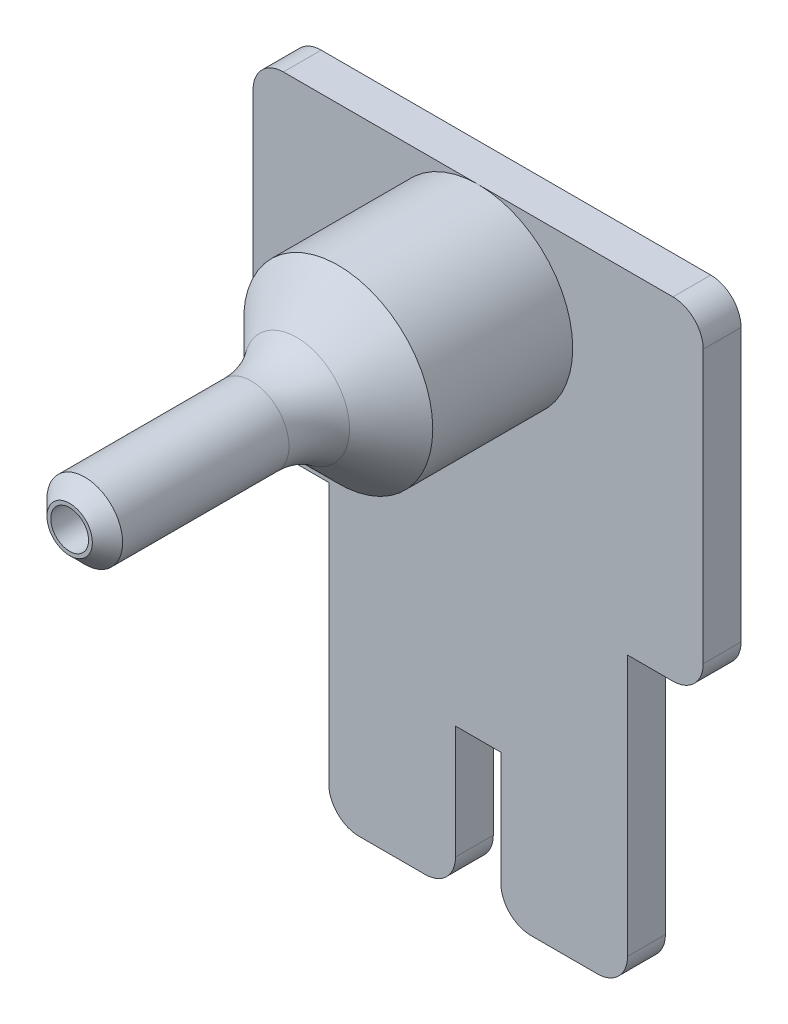
SolidWorks part; units mm, degrees
ref_plane "Alzado" through (0, 0, 0) normal (0, 0, 1) x (1, 0, 0)
ref_plane "Planta" through (0, 0, 0) normal (0, 1, 0) x (1, 0, 0)
ref_plane "Vista lateral" through (0, 0, 0) normal (1, 0, 0) x (0, 0, -1)
sketch "Croquis1" plane through (0, 0, 0) normal (0, 0, 1) x (1, 0, 0)
  line L1 (-9.875, -17.5) -> (9.875, -17.5)
  line L2 (-9.875, -17.5) -> (-9.875, 17.5)
  line L3 (-9.875, 17.5) -> (9.875, 17.5)
  line L4 (9.875, -17.5) -> (9.875, 17.5)
  line L5 (-9.875, -17.5) -> (9.875, 17.5) construction
  line L6 (-9.875, 17.5) -> (9.875, -17.5) construction
  point P0 (0, 0)
  dimension "D1" = 19.75
  dimension "D2" = 35
extrude "Saliente-Extruir1" add sketch "Croquis1" along normal blind 2.5
sketch "Croquis2" plane through (0, 0, 2.5) normal (0, 0, 1) x (1, 0, 0)
  line L0 (-9.875, -17.5) -> (9.875, -17.5) construction
  line L1 (1.5, -17.5) -> (-1.5, -17.5)
  line L2 (1.5, -17.5) -> (1.5, -8)
  line L3 (1.5, -8) -> (-1.5, -8)
  line L4 (-1.5, -17.5) -> (-1.5, -8)
  line L5 (0, -8) -> (0, 0) construction
  dimension "D1" = 9.5
  dimension "D2" = 3
extrude "Cortar-Extruir1" cut sketch "Croquis2" against normal through all
sketch "Croquis3" plane through (0, 0, 2.5) normal (0, 0, 1) x (1, 0, 0)
  line L0 (0, 0) -> (0, 1.75) construction
  line L1 (-14.875, 17.5) -> (14.875, 17.5)
  line L2 (-14.875, 17.5) -> (-14.875, 1.75)
  line L3 (-14.875, 1.75) -> (14.875, 1.75)
  line L4 (14.875, 17.5) -> (14.875, 1.75)
  line L5 (9.875, 17.5) -> (-9.875, 17.5) construction
  line L6 (1.5, -8) -> (-1.5, -8) construction
  line L7 (9.875, -17.5) -> (9.875, 17.5) construction
  dimension "D1" = 9.75
  dimension "D2" = 5
extrude "Saliente-Extruir2" add sketch "Croquis3" against normal through all
sketch "Croquis7" plane through (0, 0, 2.5) normal (0, 0, 1) x (1, 0, 0)
  line L2 (14.875, 17.5) -> (-14.875, 17.5) construction
  circle A0 centre (0, 17.5) radius 6.25
  dimension "D1" = 12.5
extrude "Saliente-Extruir4" add sketch "Croquis7" along normal blind 12 and the other way up to surface (2.5 mm away) other way up to face at (0, -3.6667, 0)
sketch "Croquis4" plane through (0, 0, 14.5) normal (0, 0, 1) x (1, 0, 0)
  circle A0 centre (0, 17.5) radius 2.5
  dimension "D1" = 5
extrude "Saliente-Extruir3" add sketch "Croquis4" along normal blind 15
sketch "Croquis5" plane through (0, 0, 29.5) normal (0, 0, 1) x (1, 0, 0)
  circle A0 centre (0, 17.5) radius 1.25
  dimension "D1" = 2.5
extrude "Cortar-Extruir2" cut sketch "Croquis5" against normal through all
sketch "Croquis10" plane through (0, 0, 0) normal (0, 0, -1) x (-1, 0, 0)
  circle A0 centre (0, 17.5) radius 4.125
  dimension "D1" = 8.25
extrude "Cortar-Extruir3" cut sketch "Croquis10" against normal blind 12
chamfer "Chaflán1" distance 1 angle 45 2 edges at (2.5, 17.5, 29.5) (-4.125, 17.5, 0)
fillet "Redondeo1" radius 2 8 edges at (-1.5, -17.5, 1.25) (1.5, -17.5, 1.25) (9.875, -17.5, 1.25) (-9.875, -17.5, 1.25) (-14.875, 1.75, 1.25) (14.875, 1.75, 1.25) (-14.875, 17.5, 1.25) (14.875, 17.5, 1.25)
chamfer "Chaflán2" distance 2.75 angle 45 2 edges at (-4.125, 17.5, 12) (6.25, 17.5, 14.5)
fillet "Redondeo2" radius 5 1 edges at (2.5, 17.5, 14.5)
sketch "Croquis11" plane through (0, 0, 0) normal (0, 0, -1) x (-1, 0, 0)
  line L0 (6.25, 17.5) -> (12.875, 17.5) construction
  line L1 (-12.875, 17.5) -> (-6.25, 17.5) construction
  line L2 (6.25, 17.5) -> (12.875, 17.5)
  line L3 (-12.875, 17.5) -> (-6.25, 17.5)
  line L4 (-14.875, 15.5) -> (-14.875, 21.75)
  line L5 (-12.875, 23.75) -> (12.875, 23.75)
  line L6 (14.875, 21.75) -> (14.875, 15.5)
  arc A0 (14.875, 15.5) -> (12.875, 17.5) centre (12.875, 15.5) ccw construction
  arc A1 (6.25, 17.5) -> (-6.25, 17.5) centre (0, 17.5) ccw construction
  arc A2 (-12.875, 17.5) -> (-14.875, 15.5) centre (-12.875, 15.5) ccw construction
  arc A3 (14.875, 15.5) -> (12.875, 17.5) centre (12.875, 15.5) ccw
  arc A4 (6.25, 17.5) -> (-6.25, 17.5) centre (0, 17.5) ccw
  arc A5 (-12.875, 17.5) -> (-14.875, 15.5) centre (-12.875, 15.5) ccw
  arc A6 (12.875, 23.75) -> (14.875, 21.75) centre (12.875, 21.75) cw
  arc A7 (-14.875, 21.75) -> (-12.875, 23.75) centre (-12.875, 21.75) cw
  arc M12 (14.875, 15.5) -> (12.875, 17.5) centre (12.875, 15.5) ccw
  line M13 (12.875, 17.5) -> (6.25, 17.5)
  arc M14 (6.25, 17.5) -> (-6.25, 17.5) centre (0, 17.5) ccw
  line M15 (-6.25, 17.5) -> (-12.875, 17.5)
  arc M16 (-12.875, 17.5) -> (-14.875, 15.5) centre (-12.875, 15.5) ccw
  dimension "D1" = 2
extrude "Saliente-Extruir5" add sketch "Croquis11" against normal up to surface (2.5 mm away) contours A7 L4 L5 M16 M15 M14 | A6 L5 L6 M14 M13 M12 region at (-9.7942, 20.7716, 0) region at (9.7942, 20.7716, 0) up to face at (0, -1.8367, 2.5)
